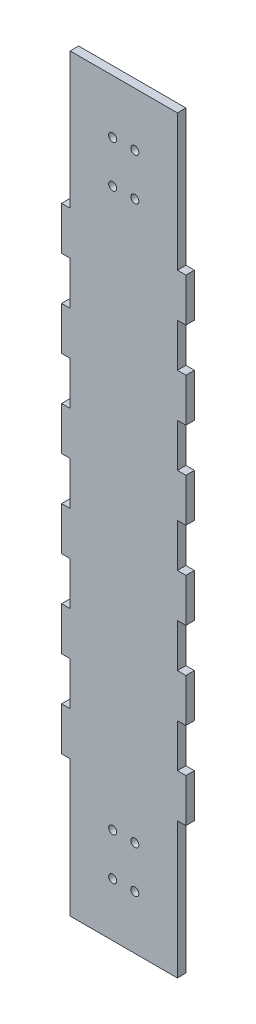
SolidWorks part; units mm, degrees
ref_plane "Front Plane" through (0, 0, 0) normal (0, 0, 1) x (1, 0, 0)
ref_plane "Top Plane" through (0, 0, 0) normal (0, 1, 0) x (1, 0, 0)
ref_plane "Right Plane" through (0, 0, 0) normal (1, 0, 0) x (0, 0, -1)
sketch "Sketch1" plane through (0, 0, 0) normal (0, 0, 1) x (1, 0, 0)
  line L5 (0, 279.4) -> (40, 279.4)
  line L87 (40, 0) -> (0, 0)
  line L88 (20, 279.4) -> (20, 0) construction
  line L89 (50.8, 139.7) -> (0, 139.7) construction
  line L90 (0, 0) -> (-3.175, 0)
  line L91 (-3.175, 0) -> (-3.175, 50.8)
  line L92 (-3.175, 50.8) -> (0, 50.8)
  line L93 (0, 50.8) -> (0, 0)
  line L94 (0, 228.6) -> (0, 279.4)
  line L95 (-3.175, 228.6) -> (0, 228.6)
  line L96 (-3.175, 279.4) -> (-3.175, 228.6)
  line L97 (0, 279.4) -> (-3.175, 279.4)
  line L98 (0, 50.8) -> (-3.175, 50.8)
  line L99 (-3.175, 50.8) -> (-3.175, 66.9636)
  line L100 (-3.175, 66.9636) -> (0, 66.9636)
  line L101 (0, 66.9636) -> (0, 50.8)
  line L102 (40, 228.6) -> (40, 279.4)
  line L103 (43.175, 228.6) -> (40, 228.6)
  line L104 (43.175, 279.4) -> (43.175, 228.6)
  line L105 (40, 279.4) -> (43.175, 279.4)
  line L106 (40, 66.9636) -> (40, 50.8)
  line L107 (43.175, 66.9636) -> (40, 66.9636)
  line L108 (43.175, 50.8) -> (43.175, 66.9636)
  line L109 (43.175, 50.8) -> (40, 50.8)
  line L110 (40, 50.8) -> (40, 0)
  line L111 (43.175, 0) -> (43.175, 50.8)
  line L112 (40, 0) -> (43.175, 0)
  line L113 (-3.175, 66.9636) -> (-3.175, 83.1273)
  line L114 (-3.175, 66.9636) -> (0, 66.9636)
  line L115 (0, 83.1273) -> (0, 66.9636)
  line L116 (-3.175, 83.1273) -> (0, 83.1273)
  line L117 (-3.175, 83.1273) -> (-3.175, 99.2909)
  line L118 (-3.175, 83.1273) -> (0, 83.1273)
  line L119 (0, 99.2909) -> (0, 83.1273)
  line L120 (-3.175, 99.2909) -> (0, 99.2909)
  line L121 (-3.175, 99.2909) -> (-3.175, 115.4545)
  line L122 (-3.175, 99.2909) -> (0, 99.2909)
  line L123 (0, 115.4545) -> (0, 99.2909)
  line L124 (-3.175, 115.4545) -> (0, 115.4545)
  line L125 (-3.175, 115.4545) -> (-3.175, 131.6182)
  line L126 (-3.175, 115.4545) -> (0, 115.4545)
  line L127 (0, 131.6182) -> (0, 115.4545)
  line L128 (-3.175, 131.6182) -> (0, 131.6182)
  line L129 (-3.175, 131.6182) -> (-3.175, 147.7818)
  line L130 (-3.175, 131.6182) -> (0, 131.6182)
  line L131 (0, 147.7818) -> (0, 131.6182)
  line L132 (-3.175, 147.7818) -> (0, 147.7818)
  line L133 (-3.175, 147.7818) -> (-3.175, 163.9455)
  line L134 (-3.175, 147.7818) -> (0, 147.7818)
  line L135 (0, 163.9455) -> (0, 147.7818)
  line L136 (-3.175, 163.9455) -> (0, 163.9455)
  line L137 (-3.175, 163.9455) -> (-3.175, 180.1091)
  line L138 (-3.175, 163.9455) -> (0, 163.9455)
  line L139 (0, 180.1091) -> (0, 163.9455)
  line L140 (-3.175, 180.1091) -> (0, 180.1091)
  line L141 (-3.175, 180.1091) -> (-3.175, 196.2727)
  line L142 (-3.175, 180.1091) -> (0, 180.1091)
  line L143 (0, 196.2727) -> (0, 180.1091)
  line L144 (-3.175, 196.2727) -> (0, 196.2727)
  line L145 (-3.175, 196.2727) -> (-3.175, 212.4364)
  line L146 (-3.175, 196.2727) -> (0, 196.2727)
  line L147 (0, 212.4364) -> (0, 196.2727)
  line L148 (-3.175, 212.4364) -> (0, 212.4364)
  line L149 (-3.175, 50.8) -> (-3.175, 66.9636) construction
  line L150 (0, 279.4) -> (0, 0)
  line L151 (43.175, 66.9636) -> (40, 66.9636)
  line L152 (40, 83.1273) -> (40, 66.9636)
  line L153 (43.175, 83.1273) -> (40, 83.1273)
  line L154 (43.175, 66.9636) -> (43.175, 83.1273)
  line L155 (43.175, 83.1273) -> (40, 83.1273)
  line L156 (40, 99.2909) -> (40, 83.1273)
  line L157 (43.175, 99.2909) -> (40, 99.2909)
  line L158 (43.175, 83.1273) -> (43.175, 99.2909)
  line L159 (43.175, 99.2909) -> (40, 99.2909)
  line L160 (40, 115.4545) -> (40, 99.2909)
  line L161 (43.175, 115.4545) -> (40, 115.4545)
  line L162 (43.175, 99.2909) -> (43.175, 115.4545)
  line L163 (43.175, 115.4545) -> (40, 115.4545)
  line L164 (40, 131.6182) -> (40, 115.4545)
  line L165 (43.175, 131.6182) -> (40, 131.6182)
  line L166 (43.175, 115.4545) -> (43.175, 131.6182)
  line L167 (43.175, 131.6182) -> (40, 131.6182)
  line L168 (40, 147.7818) -> (40, 131.6182)
  line L169 (43.175, 147.7818) -> (40, 147.7818)
  line L170 (43.175, 131.6182) -> (43.175, 147.7818)
  line L171 (43.175, 147.7818) -> (40, 147.7818)
  line L172 (40, 163.9455) -> (40, 147.7818)
  line L173 (43.175, 163.9455) -> (40, 163.9455)
  line L174 (43.175, 147.7818) -> (43.175, 163.9455)
  line L175 (43.175, 163.9455) -> (40, 163.9455)
  line L176 (40, 180.1091) -> (40, 163.9455)
  line L177 (43.175, 180.1091) -> (40, 180.1091)
  line L178 (43.175, 163.9455) -> (43.175, 180.1091)
  line L179 (43.175, 180.1091) -> (40, 180.1091)
  line L180 (40, 196.2727) -> (40, 180.1091)
  line L181 (43.175, 196.2727) -> (40, 196.2727)
  line L182 (43.175, 180.1091) -> (43.175, 196.2727)
  line L183 (43.175, 196.2727) -> (40, 196.2727)
  line L184 (40, 212.4364) -> (40, 196.2727)
  line L185 (43.175, 212.4364) -> (40, 212.4364)
  line L186 (43.175, 196.2727) -> (43.175, 212.4364)
  line L187 (43.175, 50.8) -> (43.175, 66.9636) construction
  line L188 (40, 279.4) -> (40, 50.8)
  line L189 (-3.175, 212.4364) -> (-3.175, 228.6)
  line L190 (-3.175, 212.4364) -> (0, 212.4364)
  line L191 (0, 228.6) -> (0, 212.4364)
  line L192 (-3.175, 228.6) -> (0, 228.6)
  line L193 (43.175, 212.4364) -> (40, 212.4364)
  line L194 (40, 228.6) -> (40, 212.4364)
  line L195 (43.175, 228.6) -> (40, 228.6)
  line L196 (43.175, 212.4364) -> (43.175, 228.6)
  dimension "D1" = 279.4
  dimension "D3" = 50.8
  dimension "D4" = 3.175
  dimension "D5" = 16.1636
  dimension "D7" = 16.1636
  dimension "D9" = 16.1636
  dimension "D2" = 40
  dimension "D6" = 11
  dimension "D8" = 11
extrude "Boss-Extrude1" add sketch "Sketch1" along normal blind 3.175 contours L188 L102 L5 L94 L150 L147 L143 L139 L135 L131 L127 L123 L119 L115 L101 L93 L87 L110 L106 L152 L156 L160 L164 L168 L172 L176 L180 L184 | L101 L100 L99 L92 | L120 L117 L116 L119 | L128 L125 L124 L127 | L136 L133 L132 L135 | L144 L141 L140 L143 | L189 L148 L150 L95 | L185 L196 L103 L188 | L177 L182 L181 L180 | L169 L174 L173 L172 | L161 L166 L165 L164 | L153 L158 L157 L156 | L109 L108 L107 L106
sketch "Sketch2" plane through (0, 0, 3.175) normal (0, 0, 1) x (1, 0, 0)
  line L0 (20, 0) -> (20, 279.4) construction
  line L3 (20, 139.7) -> (0, 139.7) construction
  line L4 (0, 131.6182) -> (0, 147.7818) construction
  line L5 (-3.175, 50.8) -> (-3.175, 66.9636) construction
  line L6 (40, 0) -> (0, 0) construction
  circle A0 centre (15.875, 20) radius 1.5
  circle A1 centre (15.875, 35.75) radius 1.5
  circle A2 centre (15.875, 243.65) radius 1.5
  circle A3 centre (15.875, 259.4) radius 1.5
  circle A4 centre (24.125, 259.4) radius 1.5
  circle A5 centre (24.125, 243.65) radius 1.5
  circle A6 centre (24.125, 35.75) radius 1.5
  circle A7 centre (24.125, 20) radius 1.5
  point P2 (20.2669, 7.9574)
  point P3 (20, 0)
  point P4 (-542.7994, 335.1984)
  point P16 (0, 0)
  point P30 (0, 0)
  point P31 (0, 0)
  dimension "D1" = 3
  dimension "D2" = 3
  dimension "D3" = 15.75
  dimension "D4" = 19.05
  dimension "D5" = 20
extrude "Cut-Extrude1" cut sketch "Sketch2" against normal up to surface (3.175 mm away) up to face at (20, 139.7, 0)
equation "\"D7@Sketch1\"=\"D5@Sketch1\""
equation "\"D5@Sketch1\"=((\"D1@Sketch1\"-2*\"D3@Sketch1\")/(\"D6@Sketch1\"))"
equation "\"D8@Sketch1\"=\"D6@Sketch1\""
equation "\"D9@Sketch1\"=\"D5@Sketch1\""
